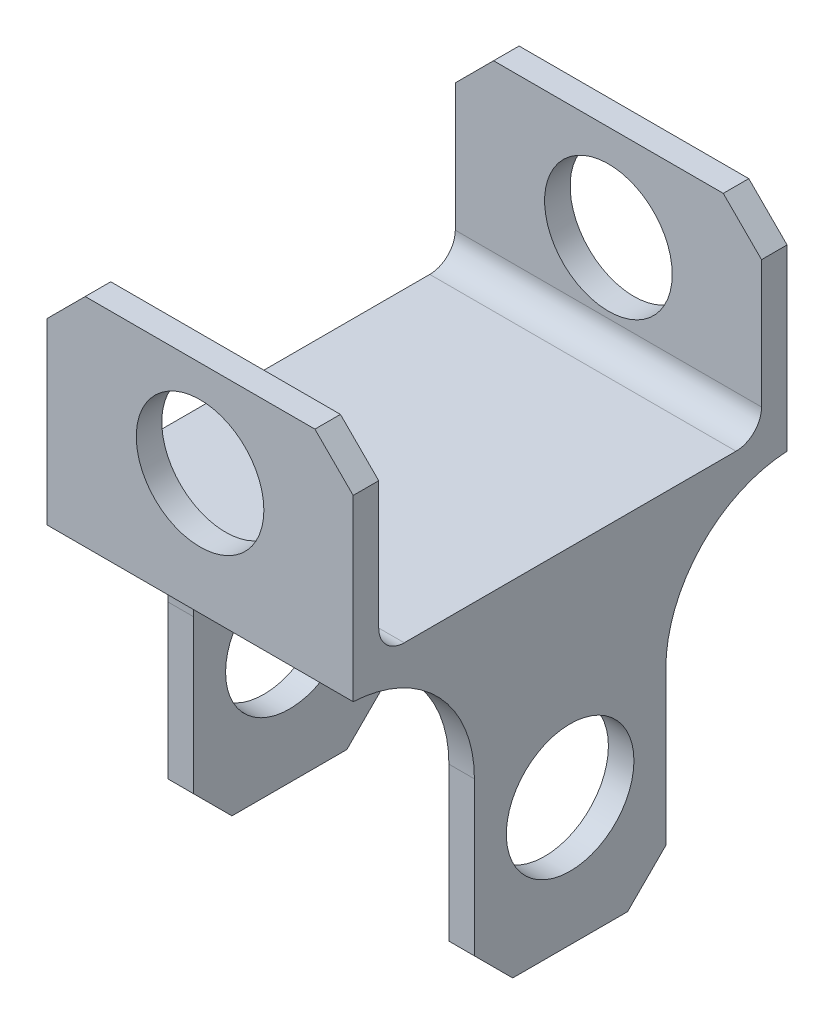
SolidWorks part; units mm, degrees
ref_plane "Front Plane" through (0, 0, 0) normal (0, 0, 1) x (1, 0, 0)
ref_plane "Top Plane" through (0, 0, 0) normal (0, 1, 0) x (1, 0, 0)
ref_plane "Right Plane" through (0, 0, 0) normal (1, 0, 0) x (0, 0, -1)
sketch "Sketch1" plane through (0, 0, 0) normal (0, 0, 1) x (1, 0, 0)
  line L1 (-12, -7.5) -> (12, -7.5)
  line L2 (-12, -7.5) -> (-12, 7.5)
  line L3 (-12, 7.5) -> (12, 7.5)
  line L4 (12, -7.5) -> (12, 7.5)
  line L5 (-12, -7.5) -> (12, 7.5) construction
  line L6 (-12, 7.5) -> (12, -7.5) construction
  line L7 (-12, -7.5) -> (12, -7.5)
  line L8 (-12, -7.5) -> (-12, -9.5)
  line L9 (-12, -9.5) -> (12, -9.5)
  line L10 (12, -7.5) -> (12, -9.5)
  circle A0 centre (0, 0) radius 5
  point P0 (0, 0)
  dimension "D1" = 10
  dimension "D2" = 15
  dimension "D3" = 24
  dimension "D4" = 2
extrude "Boss-Extrude1" add sketch "Sketch1" along normal blind 2 contours L1 L4 L3 L2 A0 | L10 L1 L8 L9 region at (-11.717, 0, 0) region at (0, -8.5, 0)
extrude "Boss-Extrude2" add sketch "Sketch1<3>" against normal blind 30 contours L10 L1 L8 L9 region at (0, -8.5, 0)
sketch "Sketch1<3>" plane through (0, 0, 0) normal (0, 0, 1) x (1, 0, 0) same geometry as "Sketch1"
ref_plane "Plane1" through (0, 0, -15) normal (0, 0, -1) x (-1, 0, 0)
mirror "Mirror1" about plane through (0, 0, -15) normal (0, 0, -1) of "Boss-Extrude1"
sketch "Sketch3" plane through (0, -9.5, 0) normal (0, -1, 0) x (1, 0, 0)
  line L0 (-12, 2) -> (12, 2) construction
  line L1 (-12, -32) -> (-10, -32)
  line L2 (-12, -32) -> (-12, 2)
  line L3 (-12, 2) -> (-10, 2)
  line L4 (-10, -32) -> (-10, 2)
  line L5 (12, -32) -> (10, -32)
  line L7 (12, -32) -> (12, 2)
  line L10 (-12, -32) -> (12, -32) construction
  line L11 (10, -32) -> (10, 2)
  line L12 (10, 2) -> (12, 2)
  dimension "D1" = 2
  dimension "D2" = 2
extrude "Boss-Extrude3" add sketch "Sketch3" along normal blind 25
sketch "Sketch4" plane through (0, -34.5, 0) normal (0, -1, 0) x (1, 0, 0)
  line L0 (-10, -32) -> (-10, 2) construction
  line L1 (-12, -32) -> (-10, -32)
  line L2 (-12, -32) -> (-12, -22.5)
  line L3 (-12, -22.5) -> (-10, -22.5)
  line L4 (-10, -32) -> (-10, -22.5)
  line L5 (-10, -32) -> (-10, 2) construction
  line L6 (-12, 2) -> (-10, 2)
  line L7 (-12, 2) -> (-12, -7.5)
  line L8 (-12, -7.5) -> (-10, -7.5)
  line L9 (-10, 2) -> (-10, -7.5)
  line L10 (12, -32) -> (12, 2) construction
  line L11 (10, 2) -> (12, 2)
  line L12 (10, 2) -> (10, -7.5)
  line L13 (10, -7.5) -> (12, -7.5)
  line L14 (12, 2) -> (12, -7.5)
  line L15 (-7.15, -15) -> (7.15, -15) construction
  line L16 (10, -32) -> (12, -32)
  line L17 (10, -32) -> (10, -22.5)
  line L18 (10, -22.5) -> (12, -22.5)
  line L19 (12, -32) -> (12, -22.5)
  dimension "D1" = 7.5
  dimension "D2" = 7.5
extrude "Cut-Extrude1" cut sketch "Sketch4" against normal blind 25
sketch "Sketch5" plane through (12, 0, 0) normal (1, 0, 0) x (0, 0, -1)
  line L0 (15, -34.5) -> (15, -7.3368) construction
  line L1 (22.5, -34.5) -> (7.5, -34.5) construction
  line L2 (15, -7.15) -> (15, 7.15) construction
  line L3 (30, -7.5) -> (0, -7.5) construction
  circle A0 centre (15, -24.5) radius 5
  dimension "D1" = 10
  dimension "D2" = 17
extrude "Cut-Extrude2" cut sketch "Sketch5" against normal blind 64.4379
fillet "Fillet1" radius 10 4 edges at (11, -9.5, -7.5) (11, -9.5, -22.5) (-11, -9.5, -22.5) (-11, -9.5, -7.5)
fillet "Fillet2" radius 2 2 edges at (0, -7.5, -30) (0, -7.5, 0)
chamfer "Chamfer1" distance 3 angle 45 8 edges at (12, 7.5, 1) (-12, 7.5, 1) (-12, 7.5, -31) (12, 7.5, -31) (-11, -34.5, -22.5) (11, -34.5, -22.5) (-11, -34.5, -7.5) (11, -34.5, -7.5)
